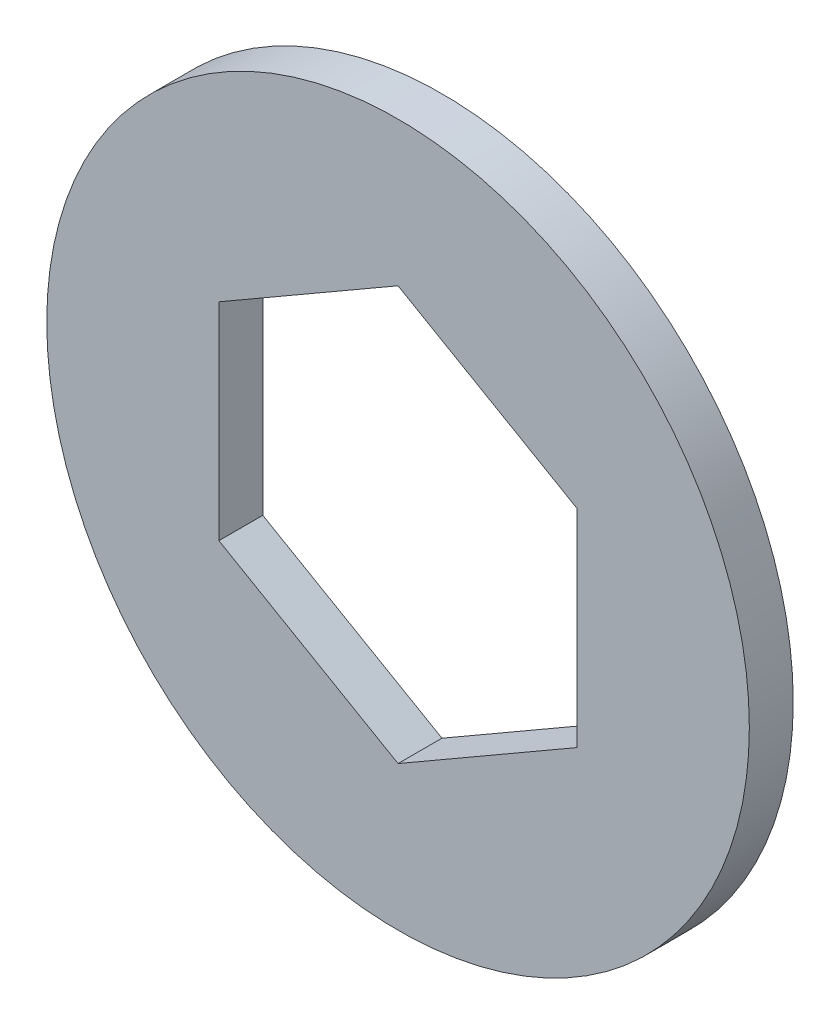
SolidWorks part; units mm, degrees
material "PET"
ref_plane "Front Plane" through (0, 0, 0) normal (0, 0, 1) x (1, 0, 0)
ref_plane "Top Plane" through (0, 0, 0) normal (0, 1, 0) x (1, 0, 0)
ref_plane "Right Plane" through (0, 0, 0) normal (1, 0, 0) x (0, 0, -1)
sketch "Sketch1" plane through (0, 0, 0) normal (0, 0, 1) x (1, 0, 0)
  line L1 (0, 7.479) -> (-6.477, 3.7395)
  line L2 (-6.477, 3.7395) -> (-6.477, -3.7395)
  line L3 (-6.477, -3.7395) -> (0, -7.479)
  line L4 (0, -7.479) -> (6.477, -3.7395)
  line L5 (6.477, -3.7395) -> (6.477, 3.7395)
  line L6 (6.477, 3.7395) -> (0, 7.479)
  circle A0 centre (0, 0) radius 12.7
  circle A1 centre (0, 0) radius 6.477 construction
  dimension "D1" = 12.954
  dimension "D2" = 25.4
extrude "Boss-Extrude1" add sketch "Sketch1" along normal mid plane 1.5875
